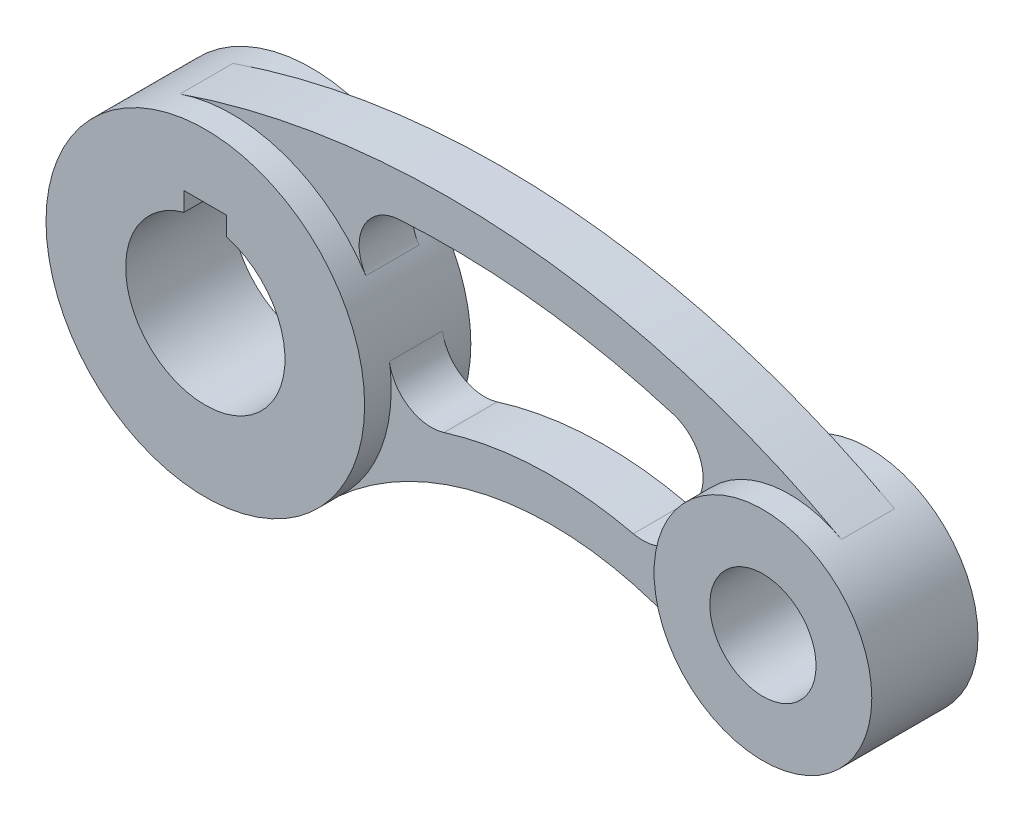
SolidWorks part; units mm, degrees
ref_plane "Front Plane" through (0, 0, 0) normal (0, 0, 1) x (1, 0, 0)
ref_plane "Top Plane" through (0, 0, 0) normal (0, 1, 0) x (1, 0, 0)
ref_plane "Right Plane" through (0, 0, 0) normal (1, 0, 0) x (0, 0, -1)
sketch "Sketch1" plane through (0, 0, 0) normal (0, 0, 1) x (1, 0, 0)
  line L0 (0, 0) -> (-105, 0) construction
  line L2 (-101, 14.4568) -> (-101, 18)
  line L3 (-101, 18) -> (-109, 18)
  line L4 (-109, 18) -> (-109, 14.4568)
  arc A0 (-11.4054, -17.0343) -> (9.7911, 18.0107) centre (0, 0) ccw
  circle A1 centre (0, 0) radius 10
  arc A2 (-114.7826, 28.3602) -> (-84.929, -22.2969) centre (-105, 0) ccw
  arc A3 (-109, 14.4568) -> (-101, 14.4568) centre (-105, 0) ccw
  arc A4 (-114.7826, 28.3602) -> (9.7911, 18.0107) centre (-64.2393, -118.1675) cw
  arc A5 (-84.929, -22.2969) -> (-11.4054, -17.0343) centre (-44.7869, -66.8908) cw
  arc A6 (-73.5448, 28.5376) -> (-21.9578, 22.6205) centre (-64.2393, -118.1675) cw
  arc A7 (-65.041, -1.9773) -> (-29.4016, -0.6542) centre (-44.7869, -66.8908) cw
  arc A8 (-75.3346, 4.4681) -> (-79.7671, 16.2266) centre (-105, 0) ccw
  arc A9 (-90.2812, -16.3511) -> (-6.9545, -10.3868) centre (-44.7869, -66.8908) cw construction
  arc A10 (-112.1739, 20.7975) -> (5.9702, 10.9821) centre (-64.2393, -118.1675) cw construction
  arc A11 (-17.4493, 10.7597) -> (-19.8466, 5.1346) centre (0, 0) ccw
  arc A12 (-73.5448, 28.5376) -> (-79.7671, 16.2266) centre (-73.0384, 20.5537) ccw
  arc A13 (-65.041, -1.9773) -> (-75.3346, 4.4681) centre (-67.4238, 5.6596) cw
  arc A14 (-29.4016, -0.6542) -> (-19.8466, 5.1346) centre (-27.5916, 7.1384) ccw
  arc A15 (-21.9578, 22.6205) -> (-17.4493, 10.7597) centre (-24.2588, 14.9586) cw
  circle A16 centre (-105, 0) radius 30
  circle A17 centre (0, 0) radius 20.5
  point P6 (-105, -15)
  point P13 (-51.4061, 36.3003)
  point P28 (-75.6709, -6.3088)
  point P33 (-9.3973, 18.2193)
  dimension "D1" = 30
  dimension "D2" = 60
  dimension "D3" = 41
  dimension "D4" = 20
  dimension "D6" = 155
  dimension "D7" = 60
  dimension "D10" = 8
  dimension "D11" = 8
  dimension "D5" = 105
  dimension "D12" = 8
  dimension "D13" = 33
  dimension "D8" = 8
  dimension "D9" = 8
extrude "Boss-Extrude1" add sketch "Sketch1" along normal blind 10 and the other way blind 10 contours A8 A16 A2 A3 L4 L3 L2 | A0 A17 A11 A1 region at (-18.6163, -7.0885, 0) region at (-130.1147, -14.8007, 0)
extrude "Boss-Extrude3" add sketch "Sketch1<5>" along normal blind 5 and the other way blind 5 contours A17 A4 A16 A12 A6 A15 | A17 A14 A7 A13 A16 A5 region at (-48.6956, -5.4031, 0) region at (-51.0613, 28.9536, 0)
sketch "Sketch1<5>" plane through (0, 0, 0) normal (0, 0, 1) x (1, 0, 0) same geometry as "Sketch1"
